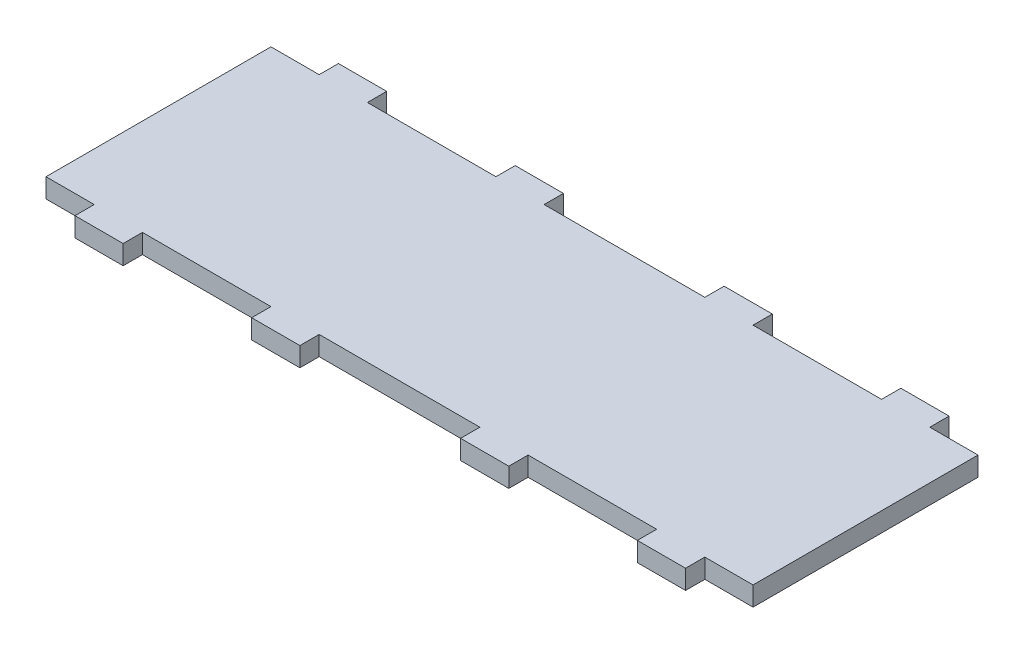
SolidWorks part; units mm, degrees
material "Acrylic (Medium-high impact)"
ref_plane "Front Plane" through (0, 0, 0) normal (0, 0, 1) x (1, 0, 0)
ref_plane "Top Plane" through (0, 0, 0) normal (0, 1, 0) x (1, 0, 0)
ref_plane "Right Plane" through (0, 0, 0) normal (1, 0, 0) x (0, 0, -1)
sketch "Sketch1" plane through (0, 0, 0) normal (0, 1, 0) x (1, 0, 0)
  line L0 (-160.3867, 60.5) -> (-145.3867, 60.5)
  line L1 (-365.3867, 60.5) -> (-350.3867, 60.5)
  line L2 (-365.3867, 60.5) -> (-365.3867, -9.5)
  line L3 (-365.3867, -9.5) -> (-350.3867, -9.5)
  line L4 (-145.3867, 60.5) -> (-145.3867, -9.5)
  line L6 (-350.3867, 60.5) -> (-350.3867, 66.5)
  line L7 (-350.3867, 66.5) -> (-335.3867, 66.5)
  line L8 (-335.3867, 60.5) -> (-335.3867, 66.5)
  line L10 (-295.3867, 60.5) -> (-295.3867, 66.5)
  line L11 (-295.3867, 66.5) -> (-280.3867, 66.5)
  line L12 (-280.3867, 60.5) -> (-280.3867, 66.5)
  line L14 (-175.3867, 60.5) -> (-175.3867, 66.5)
  line L15 (-175.3867, 66.5) -> (-160.3867, 66.5)
  line L16 (-160.3867, 60.5) -> (-160.3867, 66.5)
  line L17 (-280.3867, 60.5) -> (-230.3867, 60.5)
  line L18 (-335.3867, 60.5) -> (-295.3867, 60.5)
  line L19 (-365.3867, -15.5) -> (-350.8867, -15.5) construction
  line L21 (-350.3867, -9.5) -> (-350.3867, -15.5)
  line L22 (-350.3867, -15.5) -> (-335.3867, -15.5)
  line L23 (-335.3867, -9.5) -> (-335.3867, -15.5)
  line L25 (-295.3867, -9.5) -> (-295.3867, -15.5)
  line L26 (-295.3867, -15.5) -> (-280.3867, -15.5)
  line L27 (-280.3867, -9.5) -> (-280.3867, -15.5)
  line L29 (-175.3867, -9.5) -> (-175.3867, -15.5)
  line L30 (-175.3867, -15.5) -> (-160.3867, -15.5)
  line L31 (-160.3867, -9.5) -> (-160.3867, -15.5)
  line L32 (-335.3867, -9.5) -> (-295.3867, -9.5)
  line L33 (-280.3867, -9.5) -> (-230.3867, -9.5)
  line L34 (-160.3867, -9.5) -> (-145.3867, -9.5)
  line L35 (-215.3867, -9.5) -> (-175.3867, -9.5)
  line L37 (-230.3867, -9.5) -> (-230.3867, -15.5)
  line L38 (-230.3867, -15.5) -> (-215.3867, -15.5)
  line L39 (-215.3867, -9.5) -> (-215.3867, -15.5)
  line L40 (-215.3867, 60.5) -> (-175.3867, 60.5)
  line L42 (-230.3867, 60.5) -> (-230.3867, 66.5)
  line L43 (-230.3867, 66.5) -> (-215.3867, 66.5)
  line L44 (-215.3867, 60.5) -> (-215.3867, 66.5)
  point P34 (-255.3867, -9.5)
  dimension "D1" = 70
  dimension "D2" = 220
  dimension "D3" = 6
  dimension "D4" = 6
  dimension "D5" = 6
  dimension "D6" = 15
  dimension "D7" = 15
  dimension "D8" = 15
  dimension "D9" = 15
  dimension "D10" = 15
  dimension "D11" = 15
  dimension "D12" = 6
  dimension "D13" = 6
  dimension "D14" = 6
  dimension "D15" = 15
  dimension "D16" = 50
  dimension "D17" = 110
  dimension "D18" = 0
  dimension "D19" = 6
extrude "Boss-Extrude1" add sketch "Sketch1" along normal blind 6
